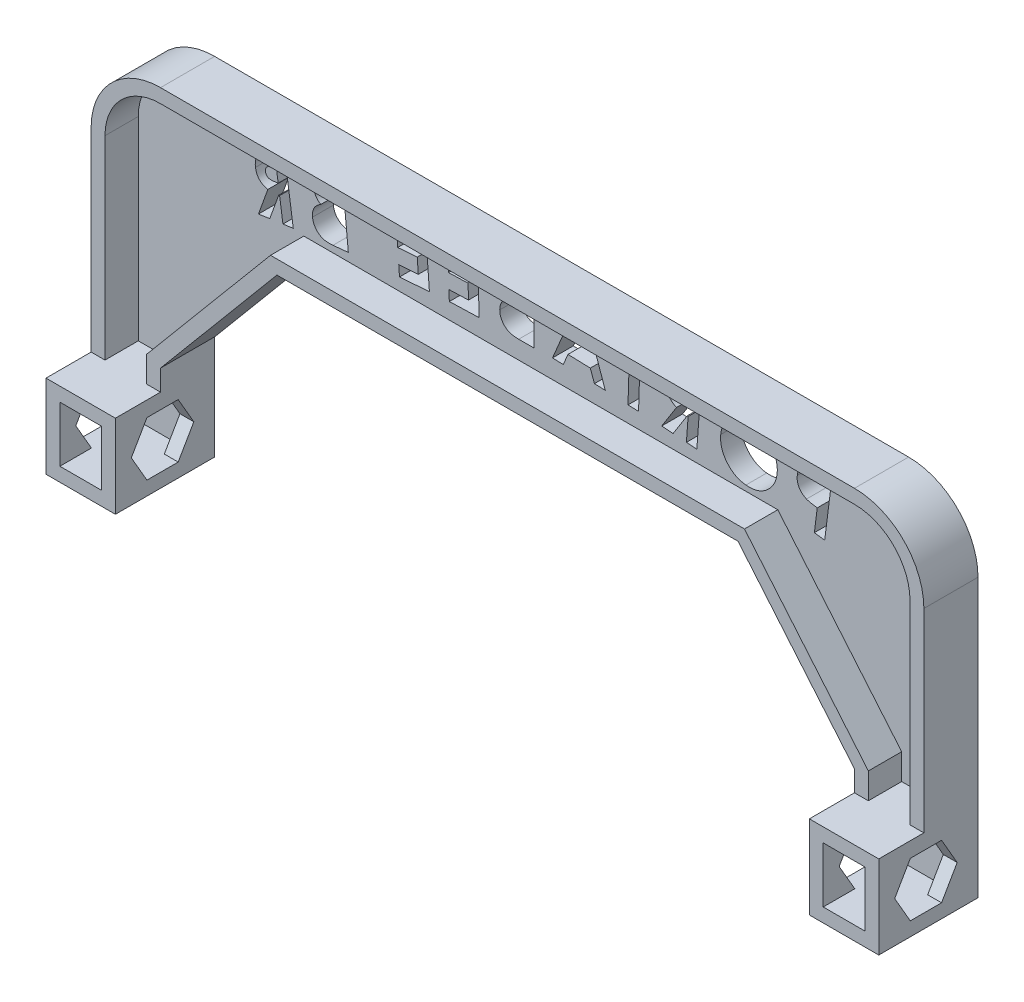
SolidWorks part; units mm, degrees
ref_plane "Plano frontal" through (0, 0, 0) normal (0, 0, 1) x (1, 0, 0)
ref_plane "Plano superior" through (0, 0, 0) normal (0, 1, 0) x (1, 0, 0)
ref_plane "Plano direito" through (0, 0, 0) normal (1, 0, 0) x (0, 0, -1)
sketch "Esboço1" plane through (0, 0, 0) normal (0, 0, 1) x (1, 0, 0)
  line L0 (-50, -35) -> (-50, -20)
  line L1 (-50, 15) -> (50, 15)
  line L2 (-60, 5) -> (-60, -35)
  line L3 (-60, -35) -> (60, -35)
  line L4 (60, 5) -> (60, -35)
  line L5 (-50, -20) -> (-33.218, 0)
  line L6 (33.218, 0) -> (50, -20)
  line L7 (-33.218, 0) -> (33.218, 0)
  line L8 (50, -20) -> (50, -35)
  line L9 (-58, 5) -> (-58, -33)
  line L10 (-58, -33) -> (58, -33)
  line L11 (58, 5) -> (58, -33)
  line L12 (-50, 13) -> (50, 13)
  line L13 (-52, -35) -> (-52, -19.2721)
  line L14 (-52, -19.2721) -> (-34.1506, 2)
  line L15 (-34.1506, 2) -> (34.1506, 2)
  line L16 (34.1506, 2) -> (52, -19.2721)
  line L17 (52, -19.2721) -> (52, -35)
  line L18 (-52, -23) -> (-58, -23)
  line L19 (50, -23) -> (60, -23)
  line L20 (-58, -25) -> (-52, -25)
  line L21 (50, -25) -> (60, -25)
  line L22 (-58, -25) -> (-60, -25)
  line L23 (-58, -23) -> (-60, -23)
  line L24 (-58, -33) -> (-60, -33)
  line L25 (-52, -23) -> (-50, -23)
  line L26 (-52, -25) -> (-50, -25)
  line L27 (58, -33) -> (60, -33)
  arc A0 (60, 5) -> (50, 15) centre (50, 5) ccw
  arc A1 (-60, 5) -> (-50, 15) centre (-50, 5) cw
  arc A2 (58, 5) -> (50, 13) centre (50, 5) ccw
  arc A3 (-58, 5) -> (-50, 13) centre (-50, 5) cw
  point P0 (0, 0)
  dimension "D10" = 10
  dimension "D1" = 120
  dimension "D2" = 10
  dimension "D3" = 10
  dimension "D4" = 35
  dimension "D5" = 130
  dimension "D6" = 15
  dimension "D7" = 15
  dimension "D8" = 15
  dimension "D9" = 130
  dimension "D12" = 2
  dimension "D13" = 8
  dimension "D11" = 2
extrude "Ressalto-extrusão1" add sketch "Esboço1" along normal blind 3 contours L9 A3 L12 A2 L11 L10 L17 L3 L4 A0 L1 A1 L2 L13 | L17 L10 L8 L3 | L21 L17 L10 L11 | L17 L16 L15 L14 L13 L10 L0 L5 L7 L6 L8 | A3 L9 L18 L13 L14 L15 L16 L17 L19 L11 A2 L12 | L17 L21 L11 L19 | L20 L9 L10 L13 | L13 L3 L0 L10 | L9 L20 L13 L18 | L27 L10 L17 L3 L4 | L11 L27 L4 L21 | L11 L21 L4 L19 | L8 L21 L17 L19 | L21 L8 L10 L17 | L24 L9 L22 L2 | L9 L23 L2 L22 | L13 L26 L0 L25 | L26 L13 L10 L0 | L10 L24 L2 L3 L13 region at (-51, -24, 0) region at (-51, -29, 0) region at (-51, -21.9304, 0) region at (-51, -34, 0) region at (-55, -24, 0) region at (-55, -29, 0) region at (0, 2.1673, 0) region at (-56, -34, 0) region at (51, -34, 0) region at (51, -29, 0) region at (-59, -24, 0) region at (-59, -29, 0) region at (-59, -21.7413, 0) region at (51, -24, 0) region at (55, -29, 0) region at (56, -34, 0) region at (55, -24, 0) region at (59, -29, 0) region at (59, -24, 0)
extrude "Ressalto-extrusão2" add sketch "Esboço1<4>" along normal blind 7.8 contours L10 L24 L2 L3 L13 | L13 L3 L0 L10 | L9 L20 L13 L18 | L13 L26 L0 L25 | L9 L23 L2 L22 | L13 L25 L0 L5 L7 L6 L8 L19 L17 L16 L15 L14 | L9 A3 L12 A2 L11 L19 L4 A0 L1 A1 L2 L23 | L11 L21 L4 L19 | L8 L21 L17 L19 | L17 L10 L8 L3 | L27 L10 L17 L3 L4 | L17 L21 L11 L19 | L26 L13 L10 L0 | L24 L9 L22 L2 | L11 L27 L4 L21 | L21 L8 L10 L17 region at (-51, -24, 0) region at (-51, -29, 0) region at (-51, -21.9304, 0) region at (-51, -34, 0) region at (-55, -24, 0) region at (-56, -34, 0) region at (51, -34, 0) region at (51, -29, 0) region at (-59, -24, 0) region at (-59, -29, 0) region at (-59, -21.7413, 0) region at (51, -24, 0) region at (56, -34, 0) region at (55, -24, 0) region at (59, -29, 0) region at (59, -24, 0)
sketch "Esboço1<4>" plane through (0, 0, 0) normal (0, 0, 1) x (1, 0, 0) same geometry as "Esboço1"
extrude "Ressalto-extrusão3" add sketch "Esboço1<5>" along normal blind 6.5 and the other way blind 1 from vertex contours L24 L9 L22 L2 | L10 L24 L2 L3 L13 | L13 L3 L0 L10 | L13 L26 L0 L25 | L9 L20 L13 L18 | L9 L23 L2 L22 | L26 L13 L10 L0 | L27 L10 L17 L3 L4 | L17 L10 L8 L3 | L21 L8 L10 L17 | L8 L21 L17 L19 | L11 L27 L4 L21 | L11 L21 L4 L19 | L17 L21 L11 L19 region at (-51, -24, 0) region at (-51, -29, 0) region at (-51, -34, 0) region at (-55, -24, 0) region at (-56, -34, 0) region at (51, -34, 0) region at (51, -29, 0) region at (-59, -24, 0) region at (-59, -29, 0) region at (51, -24, 0) region at (56, -34, 0) region at (55, -24, 0) region at (59, -29, 0) region at (59, -24, 0) starting at point (-60, -35, 7.8)
sketch "Esboço1<5>" plane through (0, 0, 0) normal (0, 0, 1) x (1, 0, 0) same geometry as "Esboço1"
sketch "Esboço2" plane through (-60, 0, 0) normal (-1, 0, 0) x (0, 0, 1)
  line L0 (14.3, -35) -> (0, -35) construction
  line L1 (5.2517, -33) -> (9.755, -33)
  line L2 (9.755, -33) -> (12.0067, -29.1)
  line L3 (12.0067, -29.1) -> (9.755, -25.2)
  line L4 (9.755, -25.2) -> (5.2517, -25.2)
  line L5 (5.2517, -25.2) -> (3, -29.1)
  line L6 (3, -29.1) -> (5.2517, -33)
  line L7 (14.3, -33) -> (3, -33) construction
  line L8 (0, 5) -> (0, -35) construction
  circle A0 centre (7.5033, -29.1) radius 3.9 construction
  dimension "D1" = 7.8
  dimension "D2" = 3
extrude "Corte-extrusão1" cut sketch "Esboço2" against normal through all
sketch "Esboço3" plane through (0, 0, 0) normal (0, 0, -1) x (-1, 0, 0)
  arc A0 (-42.764, 1.3184) -> (41.8915, 1.3184) centre (-0.4363, -268.7254) cw construction
  text T0 "PORTABEE BR" font "Century Gothic" height in points 30
extrude "Corte-extrusão2" cut sketch "Esboço3" against normal blind 90.8
delete or keep bodies "Corpo-Excluir1" type delete bodies bodies 109
delete or keep bodies "Corpo-Excluir2" type delete bodies bodies 110 112 113 114 115 116 111
sketch "Esboço4" plane through (-60, 0, 0) normal (-1, 0, 0) x (0, 0, 1)
  circle A0 centre (7.5033, -19.1) radius 3.9
sketch "Esboço5" plane through (60, 0, 0) normal (1, 0, 0) x (0, 0, -1)
  circle A0 centre (-7.5033, -19.1) radius 3.9
